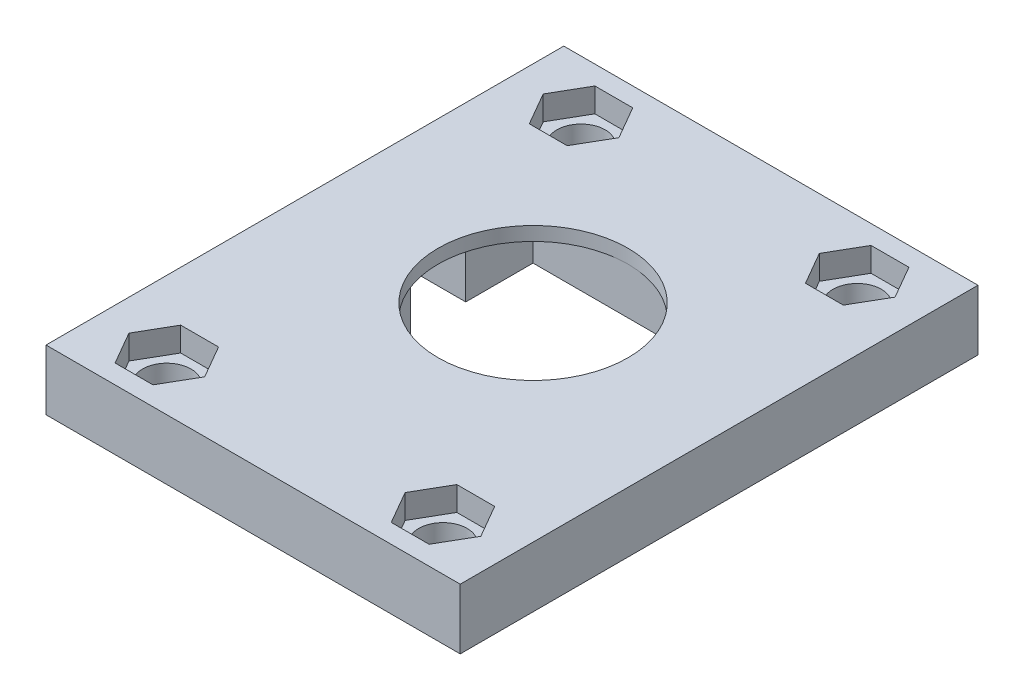
SolidWorks part; units mm, degrees
material "ABS"
ref_plane "Front Plane" through (0, 0, 0) normal (0, 0, 1) x (1, 0, 0)
ref_plane "Top Plane" through (0, 0, 0) normal (0, 1, 0) x (1, 0, 0)
ref_plane "Right Plane" through (0, 0, 0) normal (1, 0, 0) x (0, 0, -1)
sketch "Sketch1" plane through (0, 0, 0) normal (0, 1, 0) x (1, 0, 0)
  line L1 (15.24, -19.05) -> (-15.24, -19.05)
  line L2 (15.24, -19.05) -> (15.24, 19.05)
  line L3 (15.24, 19.05) -> (-15.24, 19.05)
  line L4 (-15.24, -19.05) -> (-15.24, 19.05)
  line L5 (15.24, -19.05) -> (-15.24, 19.05) construction
  line L6 (15.24, 19.05) -> (-15.24, -19.05) construction
  line L10 (-15.24, 0) -> (49984.76, 0) construction
  line L11 (0, 18.415) -> (0, -49981.585) construction
  circle A0 centre (-10.16, 15.24) radius 1.778
  circle A1 centre (10.16, 15.24) radius 1.778
  circle A2 centre (-10.16, -15.24) radius 1.778
  circle A3 centre (10.16, -15.24) radius 1.778
  point P0 (0, 0)
  point P8 (-15.24, 0)
  point P9 (15.24, 0)
  point P12 (0, 19.05)
  point P13 (0, -19.05)
  dimension "D3" = 3.556
  dimension "D4" = 30.48
  dimension "D5" = 20.32
  dimension "D1" = 38.1
  dimension "D2" = 30.48
extrude "Boss-Extrude1" add sketch "Sketch1" along normal blind 4.445
sketch "Sketch2" plane through (0, 0, 0) normal (0, -1, 0) x (1, 0, 0)
  line L0 (0, 15.24) -> (0, -49984.76) construction
  line L1 (-10.16, 15.24) -> (10.16, 15.24) construction
  line L2 (-10.16, 15.24) -> (-10.16, -15.24) construction
  line L3 (-10.16, -15.24) -> (10.16, -15.24) construction
  line L4 (10.16, 15.24) -> (10.16, -15.24) construction
  circle A0 centre (-10.16, -15.24) radius 1.778 construction
  circle A1 centre (10.16, -15.24) radius 1.778 construction
  circle A2 centre (10.16, 15.24) radius 1.778 construction
  circle A3 centre (-10.16, 15.24) radius 1.778 construction
  circle A4 centre (-10.16, -15.24) radius 1.778
  circle A5 centre (10.16, -15.24) radius 1.778
  circle A6 centre (10.16, 15.24) radius 1.778
  circle A7 centre (-10.16, 15.24) radius 1.778
  circle A8 centre (0, -1.5494) radius 6.985
  point P15 (0, -15.24)
  point P19 (0, 15.24)
  dimension "D1" = 13.97
  dimension "D2" = 13.6906
extrude "Cut-Extrude1" cut sketch "Sketch2" against normal through all
sketch "Sketch3" plane through (0, 0, 0) normal (0, -1, 0) x (1, 0, 0)
  line L0 (-6.985, -8.5344) -> (6.985, -8.5344)
  line L1 (-6.985, -8.5344) -> (-6.985, 5.4356)
  line L2 (6.985, -8.5344) -> (6.985, 5.4356)
  line L3 (-6.985, 5.4356) -> (6.985, 5.4356)
  line L4 (-6.985, -8.5344) -> (6.985, 5.4356) construction
  line L5 (6.985, -8.5344) -> (-6.985, 5.4356) construction
  line L6 (0, -8.5344) -> (0, 49991.4656) construction
  line L8 (-11.049, 0.4826) -> (-6.985, 0.4826)
  line L9 (-11.049, 0.4826) -> (-11.049, -3.5814)
  line L10 (-11.049, -3.5814) -> (-6.985, -3.5814)
  line L11 (-6.985, 0.4826) -> (-6.985, -3.5814)
  line L15 (11.049, -3.5814) -> (6.985, -3.5814)
  line L16 (6.985, 0.4826) -> (6.985, -3.5814)
  line L17 (11.049, 0.4826) -> (6.985, 0.4826)
  line L18 (11.049, 0.4826) -> (11.049, -3.5814)
  line L19 (-6.985, -1.5494) -> (49993.015, -1.5494) construction
  circle A0 centre (0, -1.5494) radius 6.985 construction
  point P3 (0, 5.4356)
  point P4 (6.985, -1.5494)
  point P13 (0, -8.5344)
  point P21 (-6.985, -1.5494)
  circle M13 centre (0, -1.5494) radius 6.985
  dimension "D1" = 4.064
  dimension "D2" = 2.032
  dimension "D3" = 2.032
extrude "Cut-Extrude2" cut sketch "Sketch3" against normal blind 3.429 contours L1 L0 M13 | L3 L1 M13 | L3 L2 M13 | L2 | L9 L10 L1 L8 | L0 L2 M13 region at (-5.4248, 0, -6.9742) region at (5.4248, 0, -6.9742) region at (-9.017, 0, -1.5494) region at (-5.4248, 0, 3.8754) region at (9.017, 0, -1.5494) region at (5.4248, 0, 3.8754)
sketch "Sketch4" plane through (0, 4.445, 0) normal (0, 1, 0) x (1, 0, 0)
  line L0 (0, -19.05) -> (0, 49980.95) construction
  line L1 (-7.3737, 15.24) -> (-8.7669, 17.653)
  line L2 (-8.7669, 17.653) -> (-11.5531, 17.653)
  line L3 (-11.5531, 17.653) -> (-12.9463, 15.24)
  line L4 (-15.24, 19.05) -> (-15.24, -19.05)
  line L5 (-15.24, -19.05) -> (15.24, -19.05)
  line L6 (15.24, -19.05) -> (15.24, 19.05)
  line L7 (15.24, 19.05) -> (-15.24, 19.05)
  line L8 (-15.24, 19.05) -> (-15.24, -19.05) construction
  line L9 (-15.24, -19.05) -> (15.24, -19.05) construction
  line L10 (15.24, -19.05) -> (15.24, 19.05) construction
  line L11 (15.24, 19.05) -> (-15.24, 19.05) construction
  line L12 (-12.9463, 15.24) -> (-11.5531, 12.827)
  line L13 (-11.5531, 12.827) -> (-8.7669, 12.827)
  line L14 (-8.7669, 12.827) -> (-7.3737, 15.24)
  line L15 (-15.24, 0) -> (49984.76, 0) construction
  line L16 (8.7669, 12.827) -> (7.3737, 15.24)
  line L17 (11.5531, 12.827) -> (8.7669, 12.827)
  line L18 (12.9463, 15.24) -> (11.5531, 12.827)
  line L19 (11.5531, 17.653) -> (12.9463, 15.24)
  line L20 (8.7669, 17.653) -> (11.5531, 17.653)
  line L21 (7.3737, 15.24) -> (8.7669, 17.653)
  line L22 (11.5531, -12.827) -> (8.7669, -12.827)
  line L23 (12.9463, -15.24) -> (11.5531, -12.827)
  line L24 (11.5531, -17.653) -> (12.9463, -15.24)
  line L25 (8.7669, -17.653) -> (11.5531, -17.653)
  line L26 (7.3737, -15.24) -> (8.7669, -17.653)
  line L27 (8.7669, -12.827) -> (7.3737, -15.24)
  line L28 (-8.7669, -12.827) -> (-7.3737, -15.24)
  line L29 (-11.5531, -12.827) -> (-8.7669, -12.827)
  line L30 (-12.9463, -15.24) -> (-11.5531, -12.827)
  line L31 (-11.5531, -17.653) -> (-12.9463, -15.24)
  line L32 (-8.7669, -17.653) -> (-11.5531, -17.653)
  line L33 (-7.3737, -15.24) -> (-8.7669, -17.653)
  circle A0 centre (-10.16, 15.24) radius 2.413 construction
  point P15 (0, -19.05)
  point P16 (0, 19.05)
  point P19 (-15.24, 0)
  point P20 (15.24, 0)
  dimension "D2" = 4.826
  dimension "D1" = 0
extrude "Cut-Extrude3" cut sketch "Sketch4" against normal blind 1.778
